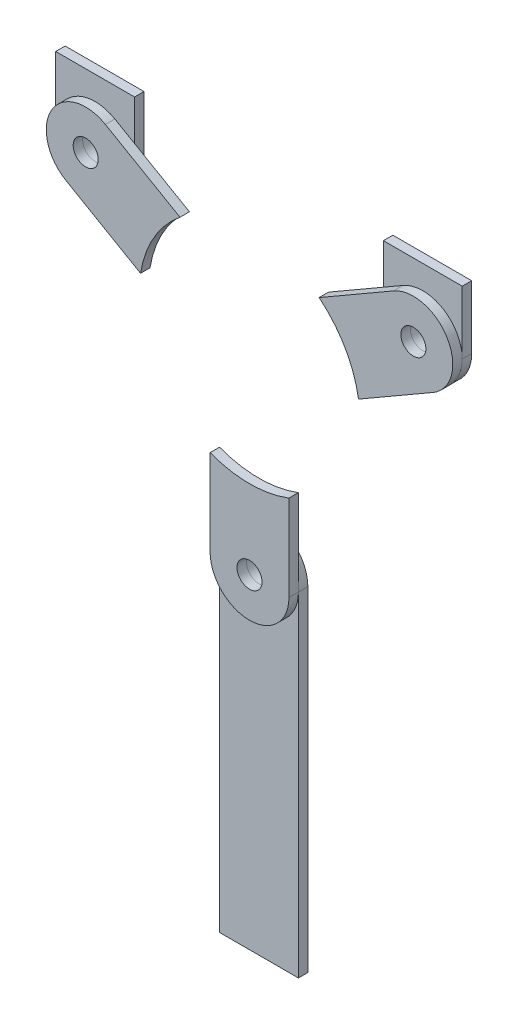
SolidWorks part; units mm, degrees
ref_plane "Front Plane" through (0, 0, 0) normal (0, 0, 1) x (1, 0, 0)
ref_plane "Top Plane" through (0, 0, 0) normal (0, 1, 0) x (1, 0, 0)
ref_plane "Right Plane" through (0, 0, 0) normal (1, 0, 0) x (0, 0, -1)
sketch "Sketch1" plane through (0, 0, 0) normal (0, 0, 1) x (1, 0, 0)
  line L0 (0, 60) -> (0, -60) construction
  line L1 (0, 0) -> (51.9615, 30) construction
  line L2 (0, 0) -> (-51.9615, 30) construction
  line L3 (45.7115, 40.8253) -> (22.0619, 27.1712)
  line L4 (58.2115, 19.1747) -> (34.5619, 5.5206)
  line L5 (12.5, -60) -> (12.5, -32.6917)
  line L6 (-12.5, -60) -> (-12.5, -32.6917)
  line L7 (-58.2115, 19.1747) -> (-34.5619, 5.5206)
  line L8 (-45.7115, 40.8253) -> (-22.0619, 27.1712)
  circle A0 centre (0, 0) radius 35 construction
  circle A1 centre (0, 0) radius 60 construction
  circle A2 centre (-51.9615, 30) radius 3.9687
  circle A3 centre (51.9615, 30) radius 3.9687
  circle A4 centre (0, -60) radius 3.9688
  arc A5 (45.7115, 40.8253) -> (58.2115, 19.1747) centre (51.9615, 30) cw
  arc A6 (22.0619, 27.1712) -> (34.5708, 5.4642) centre (0, 0) cw
  arc A7 (12.5, -60) -> (-12.5, -60) centre (0, -60) cw
  arc A8 (12.5, -32.6917) -> (-12.5533, -32.6713) centre (0, 0) cw
  arc A9 (-58.2115, 19.1747) -> (-45.7115, 40.8253) centre (-51.9615, 30) cw
  arc A10 (-34.5619, 5.5206) -> (-22.0175, 27.2071) centre (0, 0) cw
  point P31 (0, 0)
  dimension "D1" = 70
  dimension "D4" = 120
  dimension "D5" = 7.9375
  dimension "D6" = 3
  dimension "D7" = 12.5
  dimension "D2" = 60
  dimension "D3" = 60
extrude "Boss-Extrude1" add sketch "Sketch1" along normal blind 3 contours L7 A10 L8 A9 A2 | L3 A6 L4 A5 A3 | L5 A8 L6 A7 A4 region at (44.7463, 25.8343, 0) region at (0, -51.6685, 0) region at (-44.7463, 25.8343, 0)
sketch "Sketch2" plane through (0, 0, 0) normal (0, 0, 1) x (1, 0, 0)
  line L0 (-64.4615, 30) -> (-64.4615, 50)
  line L1 (-39.4615, 30) -> (-39.4615, 50)
  line L2 (-64.4615, 50) -> (-39.4615, 50)
  line L3 (0, 0) -> (0, 76.0953) construction
  line L4 (64.4615, 30) -> (64.4615, 50)
  line L5 (39.4615, 30) -> (39.4615, 50)
  line L6 (64.4615, 50) -> (39.4615, 50)
  line L7 (12.5, -60) -> (12.5, -32.6917) construction
  line L8 (-12.5, -60) -> (-12.5, -166)
  line L9 (-12.5, -166) -> (12.5, -166)
  line L10 (12.5, -166) -> (12.5, -60)
  circle A0 centre (51.9615, 30) radius 3.9688 construction
  circle A1 centre (-51.9615, 30) radius 3.9688 construction
  circle A2 centre (51.9615, 30) radius 3.9687
  circle A3 centre (-51.9615, 30) radius 3.9687
  arc A4 (-39.4615, 30) -> (-64.4615, 30) centre (-51.9615, 30) cw
  arc A5 (-45.7115, 40.8253) -> (-58.2115, 19.1747) centre (-51.9615, 30) ccw construction
  arc A6 (39.4615, 30) -> (64.4615, 30) centre (51.9615, 30) ccw
  arc A7 (-12.5, -60) -> (12.5, -60) centre (0, -60) cw
  circle A8 centre (0, -60) radius 3.9688 construction
  circle A9 centre (0, -60) radius 3.9688
  dimension "D1" = 20
  dimension "D2" = 106
extrude "Boss-Extrude2" add sketch "Sketch2" against normal blind 3 separate body
delete or keep bodies "Body-Delete1" [suppressed] type delete bodies bodies 101 102
delete or keep bodies "Body-Delete2" [suppressed] type delete bodies bodies 101 105 102 103 106
delete or keep bodies "Body-Delete3" [suppressed] type delete bodies bodies 104 105 102 101 103
